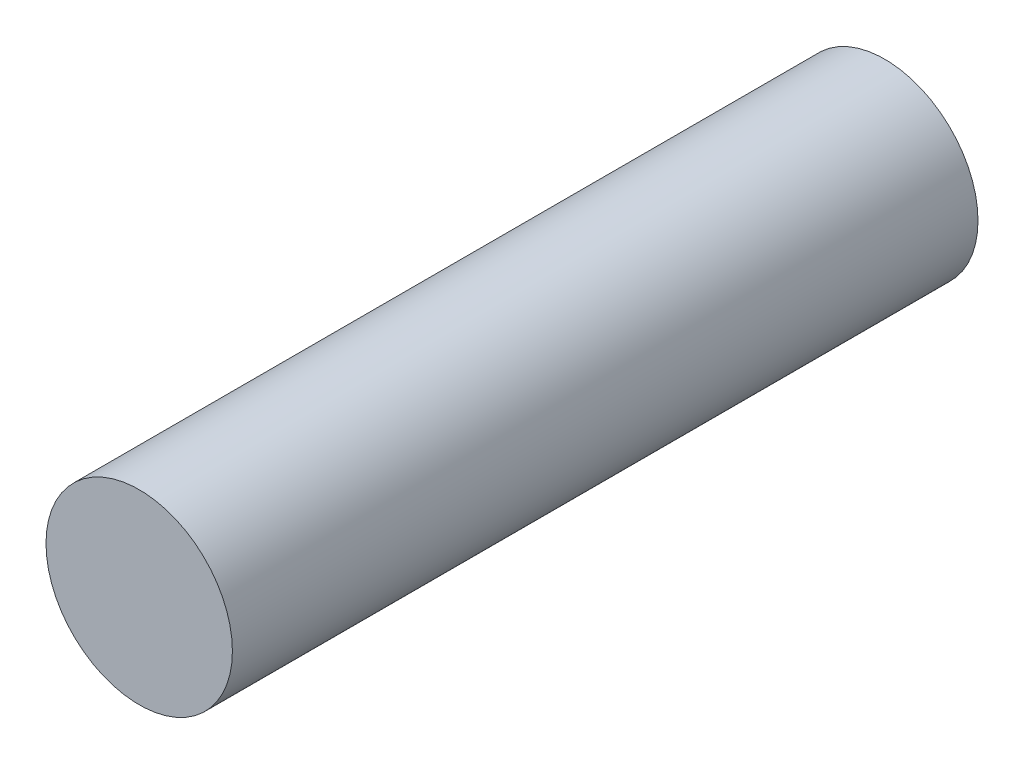
SolidWorks part; units mm, degrees
ref_plane "정면" through (0, 0, 0) normal (0, 0, 1) x (1, 0, 0)
ref_plane "윗면" through (0, 0, 0) normal (0, 1, 0) x (1, 0, 0)
ref_plane "우측면" through (0, 0, 0) normal (1, 0, 0) x (0, 0, -1)
ref_axis "기준축2" through (0, 0, 210) along (0, 0, -1)
ref_axis "기준축4" through (0, 55, 0) along (0, -1, 0)
sketch "스케치1" plane through (0, 0, 0) normal (0, 0, 1) x (1, 0, 0)
  circle A0 centre (0, 0) radius 25
  dimension "D1" = 50
extrude "보스-돌출1" add sketch "스케치1" along normal blind 200
